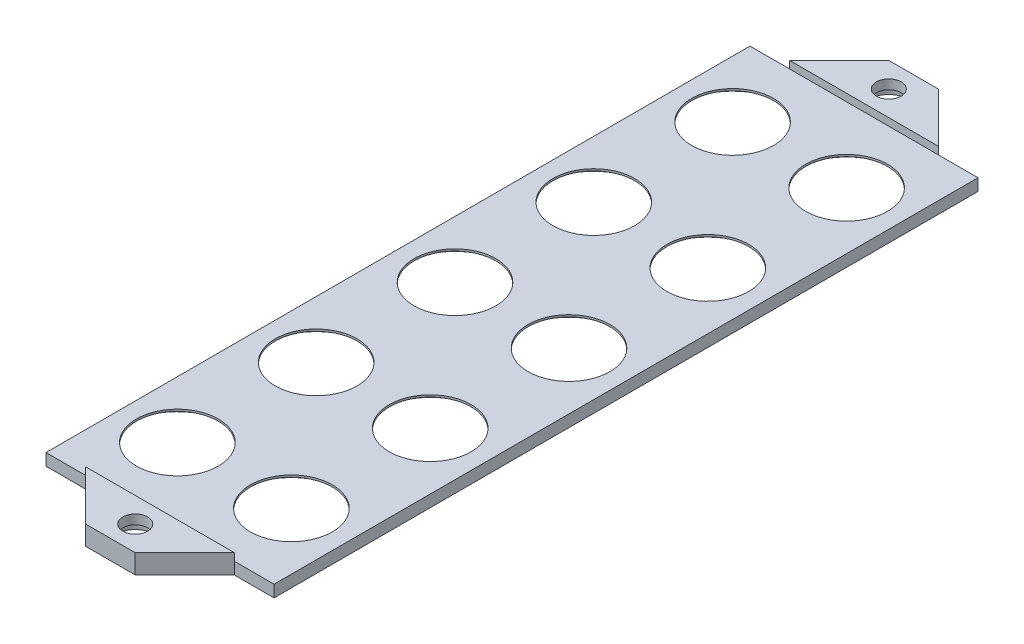
SolidWorks part; units mm, degrees
ref_plane "Front Plane" through (0, 0, 0) normal (0, 0, 1) x (1, 0, 0)
ref_plane "Top Plane" through (0, 0, 0) normal (0, 1, 0) x (1, 0, 0)
ref_plane "Right Plane" through (0, 0, 0) normal (1, 0, 0) x (0, 0, -1)
sketch "Szkic1" plane through (0, 0, 0) normal (0, 1, 0) x (1, 0, 0)
  line L0 (6.5, 25) -> (-3.5, 15)
  line L1 (-11.5, 15) -> (34.5, 15)
  line L2 (-11.5, 15) -> (-11.5, -127)
  line L3 (-11.5, -127) -> (34.5, -127)
  line L4 (34.5, 15) -> (34.5, -127)
  line L5 (6.5, 15) -> (16.5, 15)
  line L6 (6.5, 15) -> (6.5, 25)
  line L7 (6.5, 25) -> (16.5, 25)
  line L8 (16.5, 15) -> (16.5, 25)
  line L9 (16.5, 25) -> (26.5, 15)
  line L12 (-11.5, -56) -> (-33.554, -56) construction
  line L13 (16.5, -137) -> (26.5, -127)
  line L14 (16.5, -127) -> (16.5, -137)
  line L15 (6.5, -127) -> (6.5, -137)
  line L16 (6.5, -137) -> (16.5, -137)
  line L17 (6.5, -137) -> (-3.5, -127)
  line L18 (-11.5, -155) -> (34.5, -155) [skipped]
  line L19 (-11.5, -183) -> (34.5, -183) [skipped]
  circle A0 centre (0, 0) radius 8.25
  circle A1 centre (0, 0) radius 10.6
  circle A2 centre (0, 0) radius 10.1
  circle A3 centre (0, 0) radius 11
  circle A5 centre (23, 0) radius 8.25
  circle A6 centre (23, 0) radius 10.6
  circle A7 centre (23, 0) radius 10.1
  circle A8 centre (23, 0) radius 11
  circle A10 centre (23, -28) radius 8.25
  circle A11 centre (23, -28) radius 10.6
  circle A12 centre (23, -28) radius 10.1
  circle A13 centre (23, -28) radius 11
  circle A15 centre (0, -28) radius 8.25
  circle A16 centre (0, -28) radius 10.6
  circle A17 centre (0, -28) radius 10.1
  circle A18 centre (0, -28) radius 11
  circle A20 centre (0, -56) radius 11
  circle A21 centre (0, -56) radius 10.6
  circle A22 centre (0, -56) radius 10.1
  circle A23 centre (0, -56) radius 8.25
  circle A24 centre (23, -56) radius 8.25
  circle A25 centre (23, -56) radius 10.1
  circle A26 centre (23, -56) radius 10.6
  circle A27 centre (23, -56) radius 11
  circle A28 centre (0, -84) radius 11
  circle A29 centre (0, -84) radius 10.6
  circle A30 centre (0, -84) radius 10.1
  circle A31 centre (0, -84) radius 8.25
  circle A32 centre (23, -84) radius 8.25
  circle A33 centre (23, -84) radius 10.1
  circle A34 centre (23, -84) radius 10.6
  circle A35 centre (23, -84) radius 11
  circle A36 centre (0, -112) radius 11
  circle A37 centre (0, -112) radius 10.6
  circle A38 centre (0, -112) radius 10.1
  circle A39 centre (0, -112) radius 8.25
  circle A40 centre (23, -112) radius 8.25
  circle A41 centre (23, -112) radius 10.1
  circle A42 centre (23, -112) radius 10.6
  circle A43 centre (23, -112) radius 11
  dimension "D1" = 16.5
  dimension "D2" = 20.2
  dimension "D3" = 21.2
  dimension "D4" = 0.4
  dimension "D5" = 23
  dimension "D8" = 11.5
  dimension "D10" = 2
  dimension "D9" = 11.5
  dimension "D11" = 15
  dimension "D12" = 10
  dimension "D13" = 18
  dimension "D14" = 10
  dimension "D15" = 3
  dimension "D16" = 15
  dimension "D17" = 45
  dimension "D18" = 45
  dimension "D6" = 2
  dimension "D7" = 2
extrude "Dodanie-wyciągnięcie1" add sketch "Szkic1" along normal blind 0.4 contours L4 L1 L2 | L4 L2 | L2 L3 L4 | A18 | A18 A16 | A16 A17 | A17 A15 | A12 A10 | A11 A12 | A13 A11 | A13 | A7 A5 | A6 A7 | A8 A6 | A8 | A3 | A3 A1 | A1 A2 | A2 A0 | L1 L6 L0 | L1 L8 L7 L6 | L9 L8 L1 | A22 A23 | A21 A22 | A20 A21 | A25 A24 | A26 A25 | A27 A26 | A33 A32 | A34 A33 | A35 A34 | A28 A29 | A29 A30 | A30 A31 | A41 A40 | A42 A41 | A43 A42 | A38 A39 | A37 A38 | A36 A37 | L15 L16 L14 L3 | L17 L15 L3 | L3 L14 L13 region at (3.1667, 0, -18.3333) region at (11.5, 0, -20) region at (11.5, 0, 56) region at (19.8333, 0, -18.3333) region at (3.1667, 0, 130.3333) region at (11.5, 0, 132) region at (19.8333, 0, 130.3333) region at (-10.3002, 0, 0) region at (-9.8143, 0, 0) region at (-10.6889, 0, 0) region at (12.6998, 0, 0) region at (13.1857, 0, 0) region at (12.3111, 0, 0) region at (12.6998, 0, 28) region at (13.1857, 0, 28) region at (12.3111, 0, 28) region at (-10.3002, 0, 28) region at (-9.8143, 0, 28) region at (-10.6889, 0, 28) region at (-10.6889, 0, 56) region at (-10.3002, 0, 56) region at (-9.8143, 0, 56) region at (13.1857, 0, 56) region at (12.6998, 0, 56) region at (12.3111, 0, 56) region at (-10.6889, 0, 84) region at (-10.3002, 0, 84) region at (-9.8143, 0, 84) region at (13.1857, 0, 84) region at (12.6998, 0, 84) region at (12.3111, 0, 84) region at (-10.6889, 0, 112) region at (-10.3002, 0, 112) region at (-9.8143, 0, 112) region at (13.1857, 0, 112) region at (12.6998, 0, 112) region at (12.3111, 0, 112)
extrude "Dodanie-wyciągnięcie2" add sketch "Szkic1<3>" against normal blind 2 from surface contours A3 | A8 | L4 L1 L2 | L4 L2 | A18 | A13 | L2 L3 L4 | L1 L6 L0 | L1 L8 L7 L6 | L9 L8 L1 | L17 L15 L3 | L15 L16 L14 L3 | L3 L14 L13 region at (3.1667, 0, -18.3333) region at (11.5, 0, -20) region at (11.5, 0, 56) region at (19.8333, 0, -18.3333) region at (3.1667, 0, 130.3333) region at (11.5, 0, 132) region at (19.8333, 0, 130.3333) starting at face at (11.5, 0, 56)
sketch "Szkic1<3>" plane through (0, 0, 0) normal (0, 1, 0) x (1, 0, 0) same geometry as "Szkic1"
sketch "Szkic2" plane through (0, 0.4, 0) normal (0, 1, 0) x (1, 0, 0)
  line L0 (-11.5, 15) -> (34.5, 15)
  line L1 (11.5, 15) -> (11.5, 25)
  line L2 (6.5, 25) -> (16.5, 25) construction
  line L3 (-11.5, -56) -> (34.5, -56) construction
  line L4 (-11.5, 15) -> (-11.5, -127) construction
  line L5 (34.5, 15) -> (34.5, -127) construction
  circle A0 centre (11.5, 20) radius 2.5
  circle A1 centre (11.5, -132) radius 2.5
  dimension "D1" = 5
extrude "Wytnij-wyciągnięcie1" cut sketch "Szkic2" against normal blind 20 contours L1 A0 | L1 A0 | A1 region at (10.439, 0.4, -20) region at (12.561, 0.4, -20) region at (11.5, 0.4, 132)
sketch "Szkic5" plane through (0, 0.4, 0) normal (0, 1, 0) x (1, 0, 0)
  line L0 (-3.5, 15) -> (6.5, 25)
  line L1 (6.5, 25) -> (16.5, 25)
  line L2 (16.5, 25) -> (26.5, 15)
  line L3 (26.5, 15) -> (-3.5, 15)
  line L4 (-11.5, -56) -> (-35.7115, -56) construction
  line L5 (-11.5, 15) -> (-11.5, -127) construction
  line L6 (26.5, -127) -> (-3.5, -127)
  line L7 (16.5, -137) -> (26.5, -127)
  line L8 (6.5, -137) -> (16.5, -137)
  line L9 (-3.5, -127) -> (6.5, -137)
  circle A0 centre (11.5, 20) radius 2
  circle A1 centre (11.5, -132) radius 2
  circle A2 centre (11.5, -132) radius 4.15
  circle A3 centre (11.5, 20) radius 4.15
  circle M2 centre (11.5, -132) radius 2.5
  line M3 (26.5, 15) -> (16.5, 25)
  line M4 (16.5, 25) -> (6.5, 25)
  line M5 (6.5, 25) -> (-3.5, 15)
  line M9 (-3.5, -127) -> (6.5, -137)
  line M10 (6.5, -137) -> (16.5, -137)
  line M11 (16.5, -137) -> (26.5, -127)
  circle M25 centre (11.5, 20) radius 2.5
  dimension "D1" = 8.3
  dimension "D2" = 8.3
extrude "Dodanie-wyciągnięcie3" add sketch "Szkic5" along normal blind 1.5 contours L3 A3 M3 M4 M5 | L6 A2 M11 M9 M10 | A3 M25 | A2 M2 region at (1.7236, 0.4, -19.7764) region at (21.2764, 0.4, 131.7764) region at (7.4674, 0.4, 132) region at (7.4674, 0.4, -20)
extrude "Wytnij-wyciągnięcie2" cut sketch "Szkic5<3>" along normal blind 2 from surface contours A2 M2 | A3 M25 region at (7.4674, 0.4, 132) region at (7.4674, 0.4, -20) starting at face at (11.5, -2, 129.5)
sketch "Szkic5<3>" plane through (0, 0.4, 0) normal (0, 1, 0) x (1, 0, 0) same geometry as "Szkic5"
